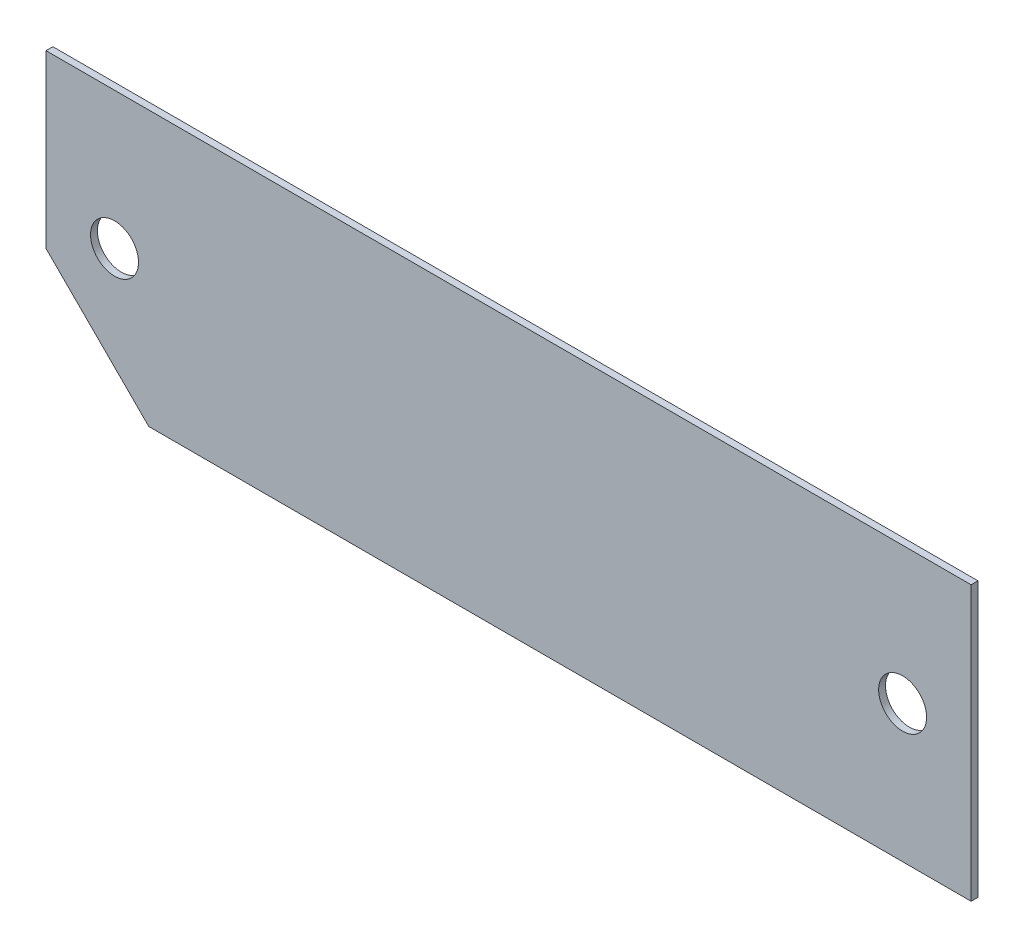
SolidWorks part; units mm, degrees
ref_plane "Спереди" through (0, 0, 0) normal (0, 0, 1) x (1, 0, 0)
ref_plane "Сверху" through (0, 0, 0) normal (0, 1, 0) x (1, 0, 0)
ref_plane "Справа" through (0, 0, 0) normal (1, 0, 0) x (0, 0, -1)
sketch "Эскиз1" plane through (0, 0, 0) normal (0, 0, 1) x (1, 0, 0)
  line L0 (0, 0) -> (0, 34.6371) construction
  line L1 (67.5, -20) -> (-67.5, -20)
  line L2 (67.5, -20) -> (67.5, 20)
  line L3 (67.5, 20) -> (-67.5, 20)
  line L4 (-67.5, -20) -> (-67.5, 20)
  line L5 (67.5, -20) -> (-67.5, 20) construction
  line L6 (67.5, 20) -> (-67.5, -20) construction
  circle A0 centre (-57.5, 0) radius 3.5
  circle A1 centre (57.5, 0) radius 3.5
  point P0 (0, 0)
  dimension "D4" = 7
  dimension "D1" = 135
  dimension "D2" = 40
  dimension "D3" = 20
  dimension "D5" = 10
base flange "Базовая кромка1" sketch "Эскиз1" thickness 1 reverse thickness direction no parameters "D1"=5
chamfer "Фаска1" distance 15 angle 45 1 edges at (-67.5, -20, -0.5)
sketch "Сгиб-Линии1" [suppressed] plane through (0, 0, 0) normal (0, 1, 0) x (1, 0, 0)
sketch "Граничная рамка1" [suppressed] plane through (0, 0, 0) normal (0, 1, 0) x (1, 0, 0)
sheet metal parameters "Листовой металл3" thickness 1 parameters "D1"=5
flat pattern "Развертка3" [suppressed]
sketch "Сгиб-Линии2" plane through (0, 0, 0) normal (0, 1, 0) x (1, 0, 0)
sketch3d "Граничная рамка2" [suppressed]
  line L0 (-67.5, -20, 0) -> (67.5, -20, 0) construction
  line L1 (-67.5, 20, 0) -> (67.5, 20, 0) construction
  line L2 (-67.5, -20, 0) -> (-67.5, 20, 0) construction
  line L3 (67.5, -20, 0) -> (67.5, 20, 0) construction
